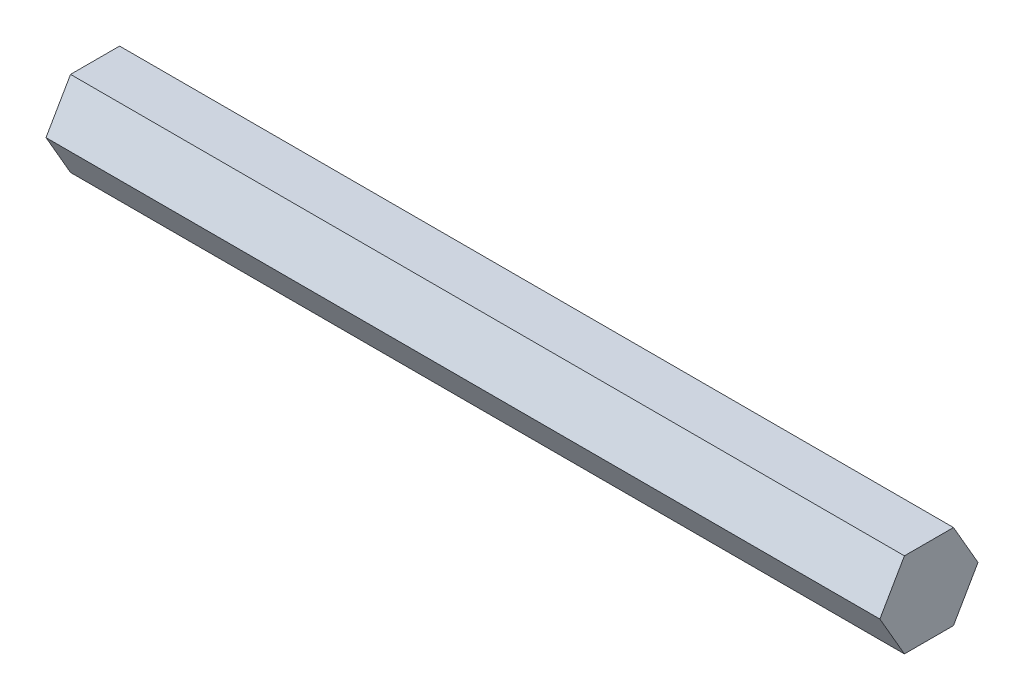
SolidWorks part; units mm, degrees
ref_plane "Alzado" through (0, 0, 0) normal (0, 0, 1) x (1, 0, 0)
ref_plane "Planta" through (0, 0, 0) normal (0, 1, 0) x (1, 0, 0)
ref_plane "Vista lateral" through (0, 0, 0) normal (1, 0, 0) x (0, 0, -1)
sketch "Croquis1" plane through (0, 0, 0) normal (1, 0, 0) x (0, 0, -1)
  line L1 (7.3323, 0) -> (3.6662, 6.35)
  line L2 (3.6662, 6.35) -> (-3.6662, 6.35)
  line L3 (-3.6662, 6.35) -> (-7.3323, 0)
  line L4 (-7.3323, 0) -> (-3.6662, -6.35)
  line L5 (-3.6662, -6.35) -> (3.6662, -6.35)
  line L6 (3.6662, -6.35) -> (7.3323, 0)
  circle A0 centre (0, 0) radius 6.35 construction
  dimension "D1" = 12.7
extrude "Saliente-Extruir1" add sketch "Croquis1" along normal blind 124.64
